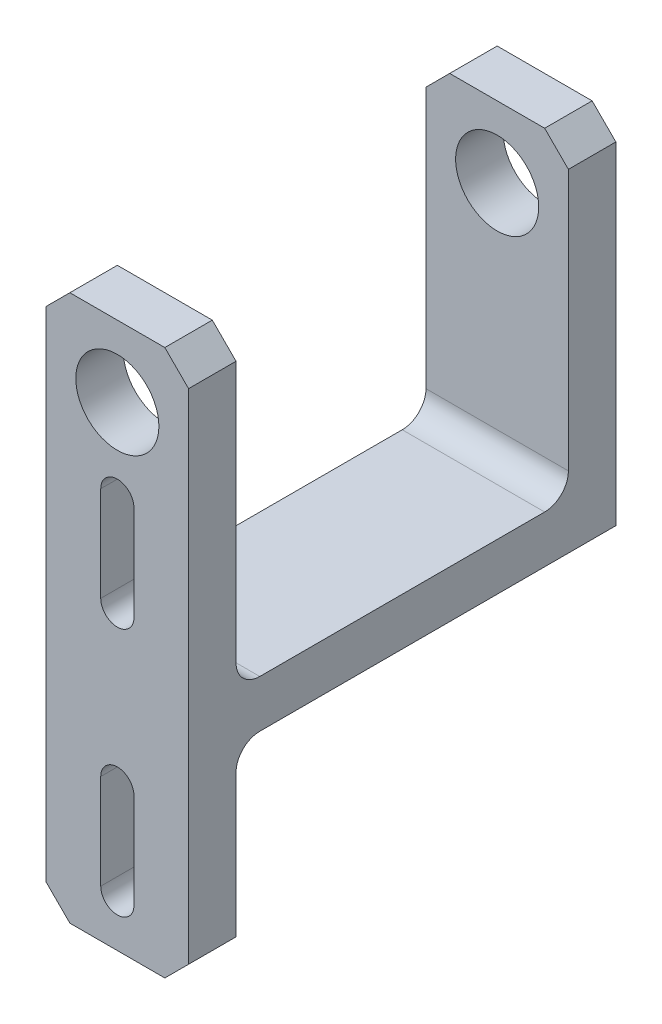
SolidWorks part; units mm, degrees
ref_plane "Front Plane" through (0, 0, 0) normal (1, 0, 0) x (0, 1, 0)
ref_plane "Top Plane" through (0, 0, 0) normal (0, 0, 1) x (0, 1, 0)
ref_plane "Right Plane" through (0, 0, 0) normal (0, 1, 0) x (-1, 0, 0)
sketch "Sketch1" plane through (0, 0, 0) normal (1, 0, 0) x (0, 1, 0)
  line L0 (0, 0) -> (0, 160)
  line L1 (-80, 160) -> (150, 160)
  line L2 (0, 0) -> (150, 0)
  point P5 (0, 0)
  dimension "D1" = 150
  dimension "D2" = 160
  dimension "D3" = 80
extrude "Extrude-Thin1" add sketch "Sketch1" along normal mid plane 60 thin thin type one direction reverse wall 20
combine bodies "Combine1" operation type add bodies to combine 102 101
fillet "Fillet1" radius 10 3 edges at (0, 20, 20) (0, 20, 160) (0, 0, 160)
sketch "Sketch3" plane through (0, 0, 180) normal (0, 0, 1) x (1, 0, 0)
  line L0 (30, 150) -> (-30, 150) construction
  circle A0 centre (0, 120) radius 17.5
  point P2 (0, 0)
  dimension "D1" = 35
  dimension "D2" = 30
extrude "Cut-Extrude1" cut sketch "Sketch3" against normal through all both and the other way through all
sketch "Sketch2" plane through (0, 0, 180) normal (0, 0, 1) x (1, 0, 0)
  line L0 (0, 85) -> (0, 45) construction
  line L1 (7, 85) -> (7, 45)
  line L2 (-7, 85) -> (-7, 45)
  line L3 (0, -20) -> (0, -60) construction
  line L4 (7, -20) -> (7, -60)
  line L5 (-7, -20) -> (-7, -60)
  arc A0 (7, 85) -> (-7, 85) centre (0, 85) ccw
  arc A1 (-7, 45) -> (7, 45) centre (0, 45) ccw
  arc A2 (7, -20) -> (-7, -20) centre (0, -20) ccw
  arc A3 (-7, -60) -> (7, -60) centre (0, -60) ccw
  circle A4 centre (0, 120) radius 17.5 construction
  point P3 (0, 65)
  point P8 (0, -40)
  dimension "D2" = 7
  dimension "D4" = 35
  dimension "D1" = 40
  dimension "D3" = 105
extrude "Cut-Extrude2" cut sketch "Sketch2" against normal up to next and the other way through all
chamfer "Chamfer1" distance 10 angle 45 6 edges at (-30, -80, 170) (30, -80, 170) (-30, 150, 10) (30, 150, 10) (-30, 150, 170) (30, 150, 170)
